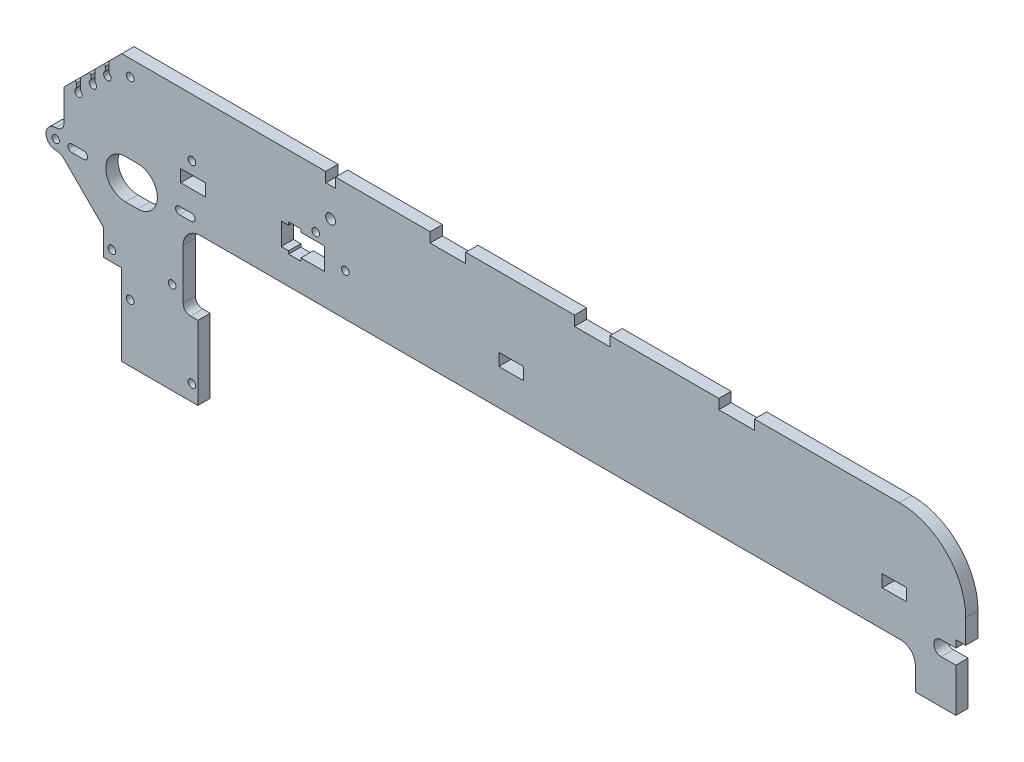
SolidWorks part; units mm, degrees
material "6061-T6 Black anodised"
ref_plane "Front Plane" through (0, 0, 0) normal (0, 0, 1) x (1, 0, 0)
ref_plane "Top Plane" through (0, 0, 0) normal (0, 1, 0) x (1, 0, 0)
ref_plane "Right Plane" through (0, 0, 0) normal (1, 0, 0) x (0, 0, -1)
sketch "Sketch1" plane through (0, 0, 0) normal (0, 0, 1) x (1, 0, 0)
  line L0 (-19.5, 0) -> (36.1968, 0) construction
  line L1 (-1.5, 32) -> (20.5, 32) construction
  line L2 (-21.9203, 0) -> (-30, 0) construction
  line L3 (-6.5, 43.5) -> (-6.5, 28.8553) construction
  line L4 (-1.5, 43.5) -> (20.5, 43.5) construction
  line L5 (310, 43.5) -> (251, 43.5)
  line L6 (21.9203, 0) -> (0, 21.9203) construction
  line L7 (0, 21.9203) -> (-21.9203, 0) construction
  line L8 (-21.9203, 0) -> (0, -21.9203) construction
  line L9 (0, -21.9203) -> (21.9203, 0) construction
  line L10 (316.5, -4.6) -> (316.5, -20)
  line L11 (-6.5, -65) -> (-6.5, -32)
  line L12 (-30, 5.3553) -> (-30, -5.3553) construction
  line L13 (327, 3.7) -> (333, 3.7)
  line L14 (316.5, -20) -> (333, -20)
  line L15 (18.5, -4.6) -> (316.5, -4.6)
  line L16 (34.5, -11.1) -> (59.432, -11.1) construction
  line L17 (333, 6.7) -> (333, 3.7)
  line L18 (9.5, 43.5) -> (9.5, -35.4767) construction
  line L19 (-1.5, 43.5) -> (20.5, 43.5) construction
  line L20 (-1.5, 43.5) -> (-1.5, 20.5) construction
  line L21 (-6.5, -65) -> (24.5, -65)
  line L22 (-1.5, 20.5) -> (20.5, 20.5) construction
  line L23 (327, -2.3) -> (333, -2.3)
  line L24 (333, -2.3) -> (333, -20)
  line L25 (333, 6.7) -> (337, 6.7)
  line L26 (337, 6.7) -> (337, 16.5)
  line L27 (18.5, -35) -> (18.5, -4.6)
  line L28 (20.5, 43.5) -> (20.5, 20.5) construction
  line L29 (17.5, 15) -> (17.5, 10)
  line L30 (17.5, 15) -> (27.5, 15)
  line L31 (27, 72.5933) -> (67, 72.5933) construction
  line L32 (147, 10) -> (157, 10)
  line L33 (147, 10) -> (147, 15)
  line L34 (17.5, 10) -> (27.5, 10)
  line L35 (27.5, 15) -> (27.5, 10)
  line L36 (147, 15) -> (157, 15)
  line L37 (157, 10) -> (157, 15)
  line L38 (303, 10) -> (313, 10)
  line L39 (303, 10) -> (303, 15)
  line L40 (303, 15) -> (313, 15)
  line L41 (313, 10) -> (313, 15)
  line L42 (27, 72.5933) -> (27, -81.6129) construction
  line L43 (27, -81.6129) -> (67, -81.6129) construction
  line L44 (67, 72.5933) -> (67, -81.6129) construction
  line L45 (-1.5, -52.5) -> (20.5, -52.5) construction
  line L46 (-1.5, -65) -> (20.5, -65) construction
  line L47 (-1.5, -65) -> (-1.5, -42) construction
  line L48 (-1.5, -42) -> (20.5, -42) construction
  line L49 (20.5, -65) -> (20.5, -42) construction
  line L50 (58.4277, 8) -> (61.4277, 8)
  line L51 (27.5, 12.5) -> (63.9277, 12.5) construction
  line L52 (61.4277, 6.8061) -> (66.4277, 6.8061)
  line L53 (61.4277, 6.8061) -> (61.4277, 8)
  line L54 (76, 8) -> (76, 17)
  line L55 (72.5, 20.1) -> (72.5, 7.1) construction
  line L56 (66.4277, 6.8061) -> (66.4277, 8)
  line L57 (66.4277, 8) -> (76, 8)
  line L58 (63.9277, 12.5) -> (76, 12.5) construction
  line L59 (66.4277, 18.1939) -> (61.4277, 18.1939)
  line L60 (66.4277, 6.8061) -> (61.4277, 18.1939) construction
  line L61 (61.4277, 6.8061) -> (66.4277, 18.1939) construction
  line L62 (18.5, -35) -> (24.5, -35)
  line L63 (66.4277, 17) -> (66.4277, 18.1939)
  line L64 (66.4277, 17) -> (76, 17)
  line L65 (61.4277, 17) -> (61.4277, 18.1939)
  line L66 (24.5, -35) -> (24.5, -65)
  line L67 (-14, -21.3553) -> (-30, -5.3553)
  line L68 (-14, -21.3553) -> (-14, -32)
  line L69 (-14, -32) -> (-6.5, -32)
  line L70 (119, 43.5) -> (119, 39.5)
  line L71 (119, 39.5) -> (133.5, 39.5)
  line L72 (177.75, 43.5) -> (177.75, 39.5)
  line L73 (119, 43.5) -> (80.5, 43.5)
  line L74 (-6.5, 28.8553) -> (-30, 5.3553) construction
  line L75 (177.75, 39.5) -> (192.25, 39.5)
  line L76 (159.788, -14) -> (-14, -14) construction
  line L77 (159.788, -14) -> (159.788, -26) construction
  line L78 (61.4277, 17) -> (58.4277, 17)
  line L79 (159.788, -26) -> (-14, -26) construction
  line L80 (-14, -14) -> (-14, -26) construction
  line L81 (58.4277, 17) -> (58.4277, 8)
  line L82 (159.788, -14) -> (-14, -26) construction
  line L83 (159.788, -26) -> (-14, -14) construction
  line L84 (192.25, 39.5) -> (192.25, 43.5)
  line L86 (236.5, 43.5) -> (236.5, 39.5)
  line L87 (236.5, 39.5) -> (251, 39.5)
  line L88 (251, 39.5) -> (251, 43.5)
  line L89 (177.75, 43.5) -> (133.5, 43.5)
  line L91 (-33.3631, 8.7185) -> (-33.3631, -8.7185) construction
  line L92 (76.5, 27.7514) -> (80.5, 27.7514) construction
  line L93 (133.5, 39.5) -> (133.5, 43.5)
  line L94 (76.5, 43.5) -> (76.5, 39.5)
  line L95 (76.5, 39.5) -> (80.5, 39.5)
  line L96 (80.5, 43.5) -> (80.5, 39.5)
  line L97 (76.5, 43.5) -> (-6.5, 43.5)
  line L98 (-30, 20) -> (-6.5, 43.5)
  line L99 (-30, 20) -> (-30, 7.3254)
  line L101 (119, 43.5) -> (177.75, 43.5) construction
  line L102 (192.25, 43.5) -> (236.5, 43.5)
  circle A0 centre (9.5, 34.5) radius 1.55 construction
  circle A1 centre (0, 0) radius 15.5 construction
  circle A2 centre (0, 21.9203) radius 1.5 construction
  circle A3 centre (21.9203, 0) radius 1.5
  circle A4 centre (0, -21.9203) radius 1.5 construction
  circle A5 centre (-21.9203, 0) radius 1.5
  circle A6 centre (0, 0) radius 5.5 construction
  arc A7 (337, 16.5) -> (310, 43.5) centre (310, 16.5) ccw
  circle A8 centre (0, 0) radius 8
  circle A9 centre (-3.05, 37) radius 1.55
  circle A10 centre (9.5, -57) radius 1.55 construction
  arc A11 (327, 3.7) -> (327, -2.3) centre (327, 0.7) ccw
  circle A12 centre (72, 0.4) radius 5 construction
  circle A13 centre (22, 38.5) radius 5 construction
  circle A14 centre (22, 38.5) radius 1.5 construction
  circle A15 centre (72, 0.4) radius 1.5 construction
  circle A16 centre (22.05, 20) radius 1.55
  circle A17 centre (-3.05, -41.5) radius 1.55
  circle A18 centre (22.05, -58.5) radius 1.55
  circle A19 centre (81.5, 20.1) radius 1.55 construction
  circle A20 centre (72.5, 20.1) radius 1.55
  circle A21 centre (84.5, 12.5) radius 1.55
  circle A22 centre (-10.5, -27.55) radius 1.55
  arc A23 (-33.3631, 3.9623) -> (-33.3631, -3.9623) centre (-33.3631, 0) ccw
  circle A24 centre (14, -27.55) radius 1.55
  circle A25 centre (-33.3631, 0) radius 1.5
  arc A26 (-33.3631, 3.9623) -> (-30, 7.3254) centre (-33.3631, 7.3254) ccw
  arc A27 (-33.3631, -3.9623) -> (-30, -5.3553) centre (-33.3631, -8.7185) cw
  circle A28 centre (78.5, 27.7514) radius 2
  point P18 (26.8692, -2.8293)
  point P19 (26.8692, 2.8293)
  point P108 (58.4277, 12.5)
  point P115 (72.894, -20)
  dimension "D2" = 31
  dimension "D3" = 3
  dimension "D4" = 11
  dimension "D12" = 16
  dimension "D20" = 3.1
  dimension "D22" = 8
  dimension "D25" = 3
  dimension "D28" = 6
  dimension "D32" = 10
  dimension "D38" = 3
  dimension "D14" = 31
  dimension "D41" = 3.1
  dimension "D44" = 9
  dimension "D45" = 3.1
  dimension "D53" = 6
  dimension "D18" = 7.5
  dimension "D57" = 3.1
  dimension "D69" = 4
  dimension "D7" = 9
  dimension "D11" = 16.5
  dimension "D17" = 15
  dimension "D8" = 65
  dimension "D9" = 43.5
  dimension "D5" = 9.5
  dimension "D6" = 4.6
  dimension "D10" = 6.5
  dimension "D13" = 337
  dimension "D15" = 23
  dimension "D16" = 25
  dimension "D19" = 30
  dimension "D21" = 9
  dimension "D23" = 21.1
  dimension "D24" = 15.4
  dimension "D26" = 6
  dimension "D27" = 4
  dimension "D29" = 67
  dimension "D30" = 17.5
  dimension "D31" = 40
  dimension "D33" = 5
  dimension "D34" = 10
  dimension "D35" = 24
  dimension "D36" = 180
  dimension "D37" = 22
  dimension "D39" = 5
  dimension "D40" = 12
  dimension "D42" = 11
  dimension "D43" = 6
  dimension "D46" = 3.1
  dimension "D47" = 9
  dimension "D48" = 15
  dimension "D49" = 0.7
  dimension "D50" = 5
  dimension "D51" = 12
  dimension "D52" = 3.5
  dimension "D54" = 4
  dimension "D55" = 12
  dimension "D56" = 20
  dimension "D58" = 4.5
  dimension "D59" = 3
  dimension "D60" = 9
  dimension "D61" = 30
  dimension "D62" = 12.5
  dimension "D63" = 52
  dimension "D64" = 14.5
  dimension "D68" = 4
  dimension "D70" = 6
  dimension "D72" = 58.75
  dimension "D67" = 3
extrude "Boss-Extrude1" add sketch "Sketch1" along normal blind 5
fillet "Fillet1" [suppressed] radius 8
fillet "Fillet2" radius 7 1 edges at (18.5, -4.6, 2.5)
fillet "Fillet3" radius 3 1 edges at (18.5, -35, 2.5)
sketch "Sketch2" plane through (0, 0, 5) normal (0, 0, 1) x (1, 0, 0)
  line L0 (21.9203, 0) -> (16.9203, 0) construction
  line L1 (21.9203, -1.5) -> (16.9203, -1.5)
  line L2 (21.9203, 1.5) -> (16.9203, 1.5)
  line L3 (0, 0) -> (-5, 0) construction
  line L4 (0, -8) -> (-5, -8)
  line L5 (0, 8) -> (-5, 8)
  line L6 (-21.9203, 0) -> (-26.9203, 0) construction
  line L7 (-21.9203, -1.5) -> (-26.9203, -1.5)
  line L8 (-21.9203, 1.5) -> (-26.9203, 1.5)
  arc A0 (21.9203, -1.5) -> (21.9203, 1.5) centre (21.9203, 0) ccw
  arc A1 (16.9203, 1.5) -> (16.9203, -1.5) centre (16.9203, 0) ccw
  arc A2 (0, -8) -> (0, 8) centre (0, 0) ccw
  arc A3 (-5, 8) -> (-5, -8) centre (-5, 0) ccw
  arc A4 (-21.9203, -1.5) -> (-21.9203, 1.5) centre (-21.9203, 0) ccw
  arc A5 (-26.9203, 1.5) -> (-26.9203, -1.5) centre (-26.9203, 0) ccw
  circle A6 centre (21.9203, 0) radius 1.5 construction
  circle A7 centre (0, 0) radius 8 construction
  point P4 (19.4203, 0)
  point P9 (-2.5, 0)
  point P16 (-24.4203, 0)
  dimension "D1" = 5
extrude "Cut-Extrude1" cut sketch "Sketch2" against normal through all
fillet "Fillet4" radius 6 1 edges at (316.5, -4.6, 2.5)
sketch "Sketch3" plane through (0, 0, 5) normal (0, 0, 1) x (1, 0, 0)
  line L0 (-12.375, 32.625) -> (-12.375, 37.625) construction
  line L1 (-13.125, 42.8359) -> (-11.625, 42.8359)
  line L2 (-13.125, 42.8359) -> (-13.125, 33.924)
  line L3 (-6.5, 43.5) -> (-30, 20) construction
  line L4 (-11.625, 42.8359) -> (-11.625, 33.924)
  line L5 (-13.125, 42.8359) -> (-11.625, 33.924) construction
  line L6 (-13.125, 33.924) -> (-11.625, 42.8359) construction
  line L7 (-6.5, 43.5) -> (-12.375, 37.625) construction
  line L8 (-12.375, 37.625) -> (-18.25, 31.75) construction
  line L9 (-18.25, 31.75) -> (-24.125, 25.875) construction
  line L10 (-24.125, 25.875) -> (-30, 20) construction
  line L11 (-17.4, 36.9218) -> (-17.4, 27.9859)
  line L12 (-18.25, 26.75) -> (-18.25, 31.75) construction
  line L13 (-19.1, 36.9218) -> (-17.4, 27.9859) construction
  line L14 (-19.1, 27.9859) -> (-17.4, 36.9218) construction
  line L15 (-19.1, 36.9218) -> (-19.1, 27.9859)
  line L16 (-19.1, 36.9218) -> (-17.4, 36.9218)
  line L17 (-23.275, 31.0468) -> (-23.275, 22.1109)
  line L18 (-24.975, 31.0468) -> (-23.275, 22.1109) construction
  line L19 (-24.975, 22.1109) -> (-23.275, 31.0468) construction
  line L20 (-24.975, 31.0468) -> (-23.275, 31.0468)
  line L21 (-24.125, 20.875) -> (-24.125, 25.875) construction
  line L22 (-24.975, 31.0468) -> (-24.975, 22.1109)
  arc A0 (-13.125, 33.924) -> (-11.625, 33.924) centre (-12.375, 32.625) ccw
  arc A1 (-19.1, 27.9859) -> (-17.4, 27.9859) centre (-18.25, 26.75) ccw
  arc A2 (-24.975, 22.1109) -> (-23.275, 22.1109) centre (-24.125, 20.875) ccw
  point P0 (-12.375, 38.3799)
  point P15 (-18.25, 32.4539)
  point P22 (-24.125, 26.5789)
  dimension "D1" = 1.5
  dimension "D2" = 1.5
  dimension "D3" = 5
extrude "Cut-Extrude2" cut sketch "Sketch3" against normal through all
fillet "Fillet5" radius 0.5 3 edges at (-24.975, 25.025, 2.5) (-19.1, 30.9, 2.5) (-13.125, 36.875, 2.5)
equation "\"y-plate-thickness\"=5"
equation "\"bed-plate-thickness\"=6"
equation "\"x-plate-thickness\"=5"
equation "\"D1@Boss-Extrude1\"=\"x-plate-thickness\""
equation "\"D33@Sketch1\"=\"x-plate-thickness\""
